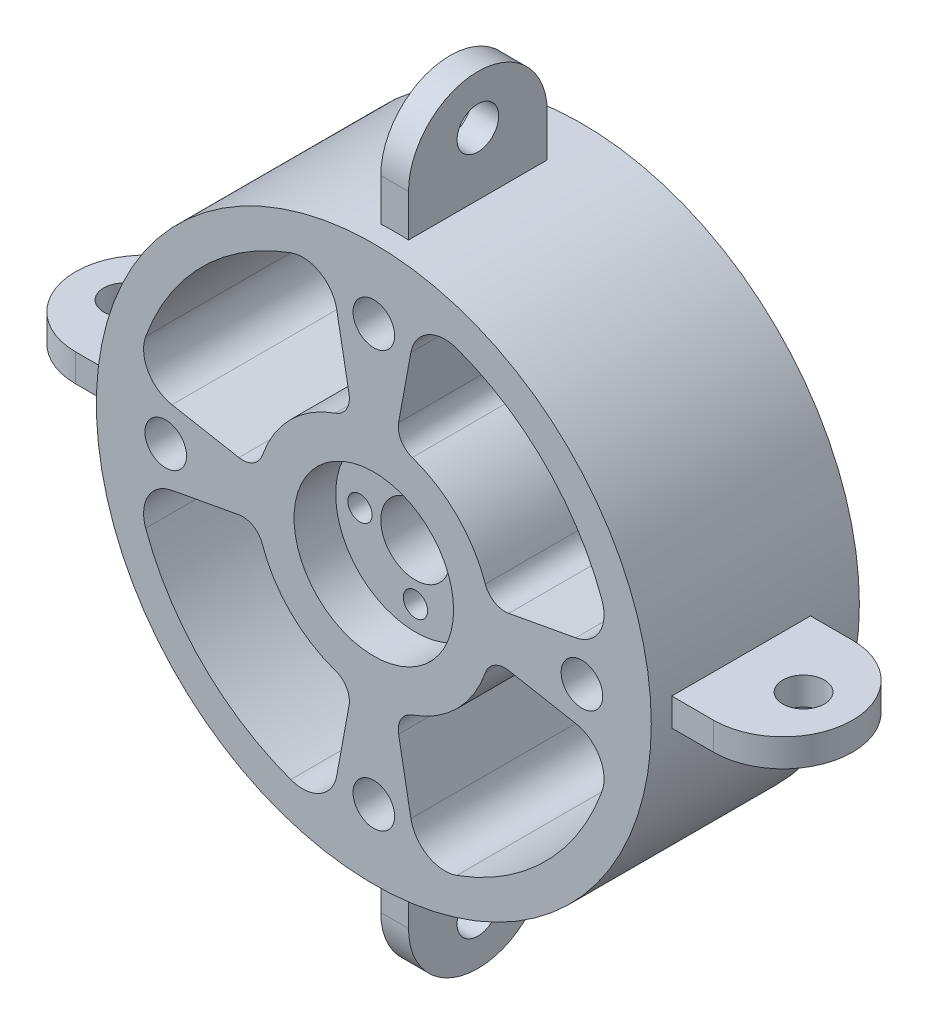
SolidWorks part; units mm, degrees
material "ABS"
ref_plane "前视基准面" through (0, 0, 0) normal (0, 0, 1) x (1, 0, 0)
ref_plane "上视基准面" through (0, 0, 0) normal (0, 1, 0) x (1, 0, 0)
ref_plane "右视基准面" through (0, 0, 0) normal (1, 0, 0) x (0, 0, -1)
sketch "草图1" plane through (0, 0, 0) normal (0, 0, 1) x (1, 0, 0)
  circle A0 centre (0, 0) radius 40
  dimension "D1" = 80
extrude "凸台-拉伸1" add sketch "草图1" along normal blind 30
sketch "草图2" plane through (0, 0, 30) normal (0, 0, 1) x (1, 0, 0)
  line L0 (0, 30) -> (0, 0) construction
  line L1 (0, 0) -> (0, -30) construction
  line L2 (-30, 0) -> (0, 0) construction
  line L3 (0, 0) -> (30, 0) construction
  circle A0 centre (30, 0) radius 3
  circle A1 centre (0, 30) radius 3
  circle A2 centre (-30, 0) radius 3
  circle A3 centre (0, -30) radius 3
  dimension "D1" = 6
  dimension "D2" = 6
  dimension "D7" = 6
  dimension "D8" = 6
  dimension "D3" = 30
  dimension "D4" = 30
  dimension "D5" = 30
  dimension "D6" = 30
extrude "切除-拉伸1" cut sketch "草图2" against normal through all
sketch "草图3" plane through (0, 0, 0) normal (1, 0, 0) x (0, 0, -1)
  line L0 (-7, 38) -> (-27, 38)
  line L1 (-27, 38) -> (-27, 46)
  line L2 (-7, 46) -> (-7, 38)
  line L3 (0, 0) -> (-35.6052, 0) construction
  arc A0 (-27, 46) -> (-7, 46) centre (-17, 46) cw
  dimension "D3" = 10
  dimension "D1" = 38
  dimension "D2" = 8
  dimension "D4" = 7
extrude "凸台-拉伸2" add sketch "草图3" along normal blind 2 and the other way blind 2
sketch "草图4" plane through (2, 0, 0) normal (1, 0, 0) x (0, 0, -1)
  line L0 (-27, 39.95) -> (-7, 39.95) construction
  line L1 (-7, 39.95) -> (-7, 46) construction
  circle A0 centre (-17, 48.95) radius 3
  dimension "D1" = 6
  dimension "D2" = 9
  dimension "D3" = 10
extrude "切除-拉伸2" cut sketch "草图4" against normal through all
pattern_circular "阵列(圆周)2" count 4 every 90 about axis through (0, 0, 30) along (0, 0, -1) of "凸台-拉伸2", "切除-拉伸2" reverse direction yes
sketch "草图5" plane through (0, 0, 0) normal (0, 0, -1) x (-1, 0, 0)
  circle A0 centre (0, 0) radius 5
  dimension "D1" = 10
extrude "切除-拉伸3" cut sketch "草图5" against normal up to next
sketch "草图6" plane through (0, 0, 30) normal (0, 0, 1) x (1, 0, 0)
  circle A0 centre (0, 0) radius 11.5
  dimension "D1" = 23
extrude "切除-拉伸4" cut sketch "草图6" against normal blind 6
sketch "草图7" plane through (0, 0, 24) normal (0, 0, 1) x (1, 0, 0)
  circle A0 centre (0, 0) radius 8 construction
  circle A1 centre (-8, 0) radius 1.75
  circle A2 centre (0, 8) radius 1.75
  circle A3 centre (8, 0) radius 1.75
  circle A4 centre (0, -8) radius 1.75
  dimension "D1" = 16
  dimension "D2" = 3.5
  dimension "D3" = 3.5
  dimension "D4" = 3.5
  dimension "D5" = 3.5
extrude "切除-拉伸5" cut sketch "草图7" against normal up to next
sketch "草图8" plane through (0, 0, 30) normal (0, 0, 1) x (1, 0, 0)
  line L0 (-28.1908, 10.2606) -> (0, 0) construction
  line L1 (0, 0) -> (-10.2606, 28.1908) construction
  line L2 (0, 0) -> (-30, 0) construction
  line L3 (-28.1908, 10.2606) -> (-32.8892, 11.9707) construction
  line L4 (-10.2606, 28.1908) -> (-11.9707, 32.8892) construction
  line L5 (-19.4485, 3.5715) -> (-29.0939, 5.3428)
  line L6 (-3.5715, 19.4485) -> (-5.3428, 29.0939)
  line L7 (19.4485, 3.5715) -> (29.0939, 5.3428)
  line L8 (3.5715, 19.4485) -> (5.3428, 29.0939)
  line L9 (3.5715, -19.4485) -> (5.3428, -29.0939)
  line L10 (19.4485, -3.5715) -> (29.0939, -5.3428)
  line L11 (-19.4485, -3.5715) -> (-29.0939, -5.3428)
  line L12 (-3.5715, -19.4485) -> (-5.3428, -29.0939)
  arc A0 (-28.1908, 10.2606) -> (-10.2606, 28.1908) centre (0, 0) cw construction
  arc A6 (-32.8892, 11.9707) -> (-11.9707, 32.8892) centre (0, 0) cw
  arc A7 (-32.8892, 11.9707) -> (-29.0939, 5.3428) centre (-28.1908, 10.2606) ccw
  arc A8 (-11.9707, 32.8892) -> (-5.3428, 29.0939) centre (-10.2606, 28.1908) cw
  arc A9 (-16.0706, 5.5439) -> (-5.5439, 16.0706) centre (0, 0) cw
  arc A10 (-5.5439, 16.0706) -> (-3.5715, 19.4485) centre (-6.5222, 18.9066) ccw
  arc A11 (-16.0706, 5.5439) -> (-19.4485, 3.5715) centre (-18.9066, 6.5222) cw
  arc A12 (11.9707, 32.8892) -> (32.8892, 11.9707) centre (0, 0) cw
  arc A13 (32.8892, 11.9707) -> (29.0939, 5.3428) centre (28.1908, 10.2606) cw
  arc A14 (16.0706, 5.5439) -> (19.4485, 3.5715) centre (18.9066, 6.5222) ccw
  arc A15 (5.5439, 16.0706) -> (16.0706, 5.5439) centre (0, 0) cw
  arc A16 (5.5439, 16.0706) -> (3.5715, 19.4485) centre (6.5222, 18.9066) cw
  arc A17 (11.9707, 32.8892) -> (5.3428, 29.0939) centre (10.2606, 28.1908) ccw
  arc A18 (32.8892, -11.9707) -> (11.9707, -32.8892) centre (0, 0) cw
  arc A19 (11.9707, -32.8892) -> (5.3428, -29.0939) centre (10.2606, -28.1908) cw
  arc A20 (5.5439, -16.0706) -> (3.5715, -19.4485) centre (6.5222, -18.9066) ccw
  arc A21 (16.0706, -5.5439) -> (5.5439, -16.0706) centre (0, 0) cw
  arc A22 (16.0706, -5.5439) -> (19.4485, -3.5715) centre (18.9066, -6.5222) cw
  arc A23 (32.8892, -11.9707) -> (29.0939, -5.3428) centre (28.1908, -10.2606) ccw
  arc A24 (-11.9707, -32.8892) -> (-32.8892, -11.9707) centre (0, 0) cw
  arc A25 (-32.8892, -11.9707) -> (-29.0939, -5.3428) centre (-28.1908, -10.2606) cw
  arc A26 (-16.0706, -5.5439) -> (-19.4485, -3.5715) centre (-18.9066, -6.5222) ccw
  arc A27 (-5.5439, -16.0706) -> (-16.0706, -5.5439) centre (0, 0) cw
  arc A28 (-5.5439, -16.0706) -> (-3.5715, -19.4485) centre (-6.5222, -18.9066) cw
  arc A29 (-11.9707, -32.8892) -> (-5.3428, -29.0939) centre (-10.2606, -28.1908) ccw
  dimension "D2" = 20
  dimension "D3" = 30
  dimension "D4" = 35
  dimension "D5" = 17
  dimension "D6" = 3
  dimension "D1" = 50
  dimension "D7" = 4
extrude "切除-拉伸6" cut sketch "草图8" against normal up to next
